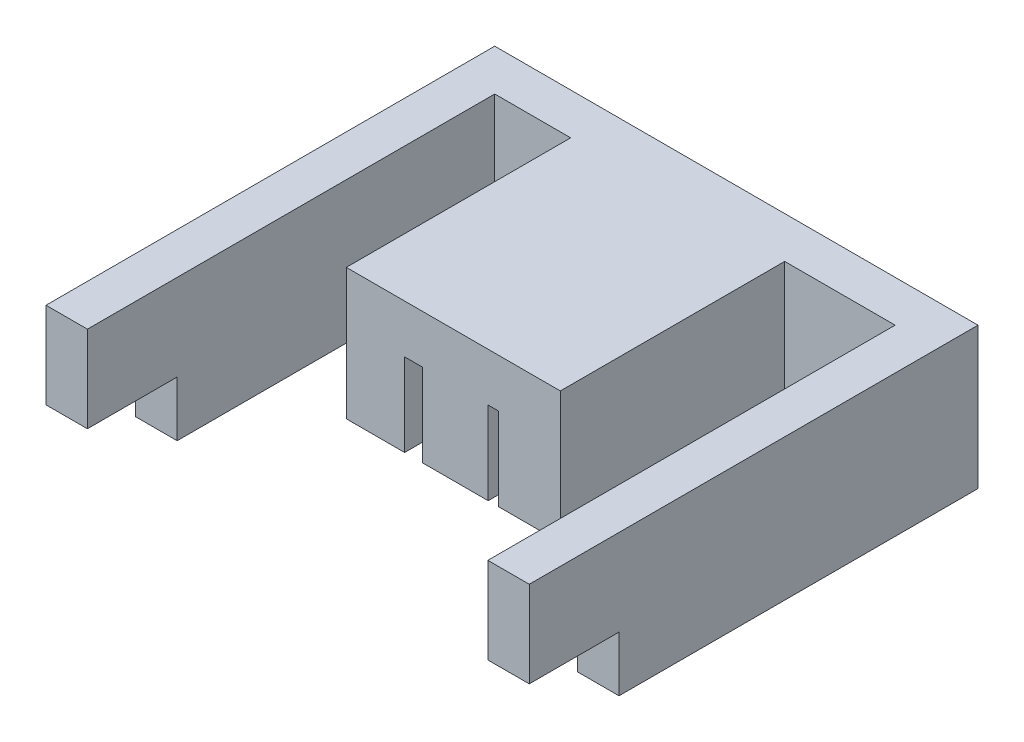
SolidWorks part; units mm, degrees
material "PBT General Purpose"
ref_plane "Front Plane" through (0, 0, 0) normal (0, 0, 1) x (1, 0, 0)
ref_plane "Top Plane" through (0, 0, 0) normal (0, 1, 0) x (1, 0, 0)
ref_plane "Right Plane" through (0, 0, 0) normal (1, 0, 0) x (0, 0, -1)
sketch "Sketch1" plane through (0, 0, 0) normal (0, 1, 0) x (1, 0, 0)
  line L0 (29, -32.5) -> (35, -32.5)
  line L1 (-35, 32.5) -> (35, 32.5)
  line L2 (-35, 32.5) -> (-35, -32.5)
  line L3 (-35, -32.5) -> (-29, -32.5)
  line L4 (35, 32.5) -> (35, -32.5)
  line L5 (-29, 26.5) -> (29, 26.5)
  line L6 (-29, 26.5) -> (-29, -32.5)
  line L8 (29, 26.5) -> (29, -32.5)
  point P8 (0, 26.5)
  point P10 (-35, 0)
  dimension "D1" = 70
  dimension "D2" = 65
  dimension "D3" = 6
  dimension "D4" = 6
  dimension "D5" = 6
extrude "Boss-Extrude1" add sketch "Sketch1" along normal blind 20.5
sketch "Sketch2" plane through (0, 0, 0) normal (0, -1, 0) x (1, 0, 0)
  line L0 (35, 32.5) -> (35, -32.5) construction
  line L1 (29, 32.5) -> (35, 32.5)
  line L2 (29, 32.5) -> (29, 19.5)
  line L3 (29, 19.5) -> (35, 19.5)
  line L4 (35, 32.5) -> (35, 19.5)
  line L5 (0, -1000) -> (0, 49000) construction
  line L6 (-29, -26.5) -> (29, -26.5) construction
  line L7 (-12.5, -26.5) -> (12.5, -26.5)
  line L8 (-12.5, -26.5) -> (-12.5, -32.5)
  line L9 (-12.5, -32.5) -> (12.5, -32.5)
  line L10 (12.5, -26.5) -> (12.5, -32.5)
  line L11 (35, -32.5) -> (-35, -32.5) construction
  line L12 (-29, 19.5) -> (-35, 19.5)
  line L13 (-35, 32.5) -> (-35, 19.5)
  line L14 (-29, 32.5) -> (-35, 32.5)
  line L15 (-29, 32.5) -> (-29, 19.5)
  point P18 (0, -26.5)
  point P19 (0, -26.5)
  dimension "D1" = 13
  dimension "D2" = 25
extrude "Cut-Extrude1" cut sketch "Sketch2" against normal blind 8
sketch "Sketch3" plane through (0, 20.5, 0) normal (0, 1, 0) x (1, 0, 0)
  line L0 (-29, -32.5) -> (-29, 26.5) construction
  line L1 (-14, 21) -> (9, 21)
  line L2 (-14, 21) -> (-14, -2)
  line L3 (-14, -2) -> (9, -2)
  line L4 (9, 21) -> (9, -2)
  line L5 (-29, 26.5) -> (29, 26.5) construction
  dimension "D1" = 23
  dimension "D2" = 23
  dimension "D3" = 15
  dimension "D4" = 5.5
extrude "Boss-Extrude2" add sketch "Sketch3" against normal offset from surface (7 mm away) 13.5 separate body up to face at (-25.5, 0, -13.1667)
sketch "Sketch4" plane through (0, 20.5, 0) normal (0, 1, 0) x (1, 0, 0)
  line L0 (-18, 26.5) -> (-18, -6)
  line L1 (-29, 26.5) -> (29, 26.5) construction
  line L2 (-18, -6) -> (13, -6)
  line L3 (13, -6) -> (13, 26.5)
  line L4 (-14, 21) -> (-14, -2)
  line L5 (-14, -2) -> (9, -2)
  line L6 (9, -2) -> (9, 21)
  line L7 (9, 21) -> (-14, 21)
  line L8 (-14, 21) -> (-14, -2)
  line L9 (-14, -2) -> (9, -2)
  line L10 (9, -2) -> (9, 21)
  line L11 (9, 21) -> (-14, 21)
  line L12 (13, 26.5) -> (-18, 26.5)
  line M12 (-29, 26.5) -> (29, 26.5)
  dimension "D2" = 4
  dimension "D3" = 4
  dimension "D4" = 4
  dimension "D1" = 0
extrude "Boss-Extrude4" add sketch "Sketch4" against normal offset from surface (19 mm away) 12 contours L2 L3 L0 L11 L10 L9 L8 M12 region at (-2.5, 20.5, -26.0509) up to face at (-2.5, 13.5, -9.5) offset beyond the face yes
sketch "Sketch5" plane through (0, 1.5, 0) normal (0, -1, 0) x (1, 0, 0)
  line L0 (-14, -21) -> (9, -21) construction
  line L1 (-6.95, -21) -> (-9.55, -21)
  line L2 (-6.95, -21) -> (-6.95, -26.5)
  line L3 (-6.95, -26.5) -> (-9.55, -26.5)
  line L4 (-9.55, -21) -> (-9.55, -26.5)
  line L5 (12.5, -26.5) -> (-12.5, -26.5) construction
  line L6 (9, 2) -> (-14, 2) construction
  line L7 (-9.55, 2) -> (-6.95, 2)
  line L8 (-9.55, 2) -> (-9.55, 6)
  line L9 (-9.55, 6) -> (-6.95, 6)
  line L10 (-6.95, 2) -> (-6.95, 6)
  line L11 (13, 6) -> (-18, 6) construction
  line L12 (-18, 6) -> (-18, -26.5) construction
  line L13 (-18, 2) -> (-14, 2)
  line L14 (-18, 2) -> (-18, -13)
  line L15 (-18, -13) -> (-14, -13)
  line L16 (-14, 2) -> (-14, -13)
  line L17 (-14, 2) -> (-14, -21) construction
  line L18 (9, 2) -> (-14, 2) construction
  line L19 (2.55, 6) -> (4.05, 6)
  line L20 (2.55, 6) -> (2.55, 2)
  line L21 (2.55, 2) -> (4.05, 2)
  line L22 (4.05, 6) -> (4.05, 2)
  line L23 (-14, 2) -> (-14, -21) construction
  dimension "D1" = 1.5
  dimension "D2" = 9.5
  dimension "D3" = 15
  dimension "D4" = 2.6
  dimension "D5" = 4.45
extrude "Cut-Extrude2" cut sketch "Sketch5" against normal up to surface (12 mm away) up to face at (-2.5, 13.5, -9.5)
sketch "Sketch6" plane through (0, 0, 0) normal (0, -1, 0) x (1, 0, 0)
  line L1 (-35, 19.5) -> (-29, 19.5) construction
  line L2 (-29, -26.5) -> (-12.5, -26.5) construction
  circle A0 centre (-32, 14.5) radius 1.5
  circle A1 centre (-32, -21.5) radius 1.5
  point P6 (-32, 19.5)
  dimension "D1" = 3
  dimension "D3" = 3
  dimension "D2" = 5
  dimension "D4" = 5
extrude "Cut-Extrude3" cut sketch "Sketch6" against normal blind 10
mirror "Mirror1" about plane through (0, 0, 0) normal (1, 0, 0) of "Cut-Extrude3"
equation "\"body_height\"= 41mm"
equation "\"D1@Boss-Extrude1\"=\"body_height\" / 2"
equation "\"D1@Boss-Extrude2\"=12+1.5"
